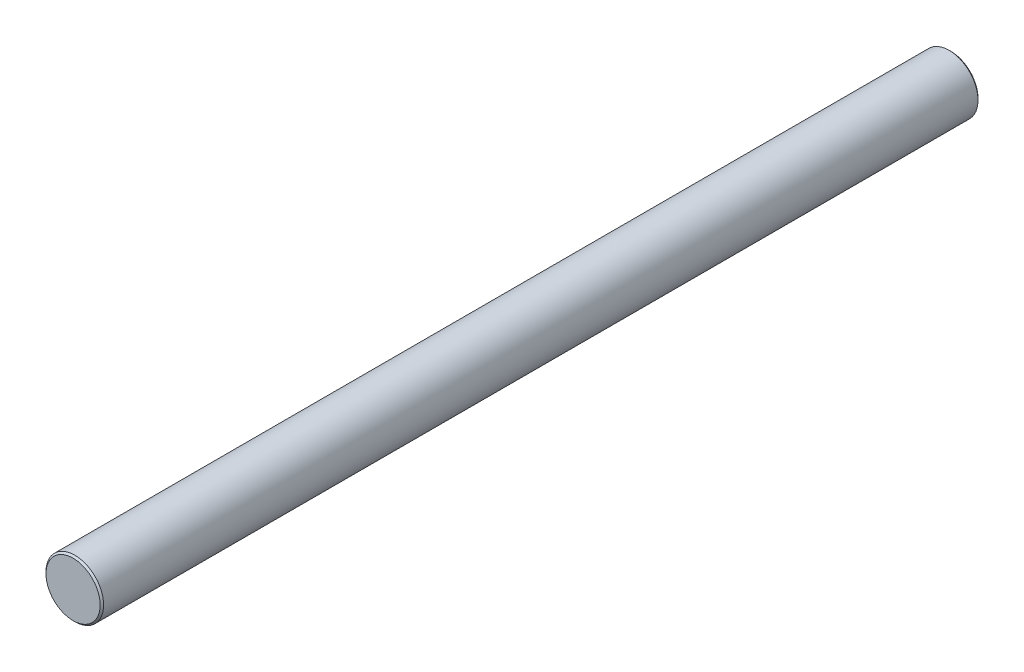
SolidWorks part; units mm, degrees
material "Alloy Steel"
ref_plane "Front Plane" through (0, 0, 0) normal (0, 0, 1) x (1, 0, 0)
ref_plane "Top Plane" through (0, 0, 0) normal (0, 1, 0) x (1, 0, 0)
ref_plane "Right Plane" through (0, 0, 0) normal (1, 0, 0) x (0, 0, -1)
sketch "Sketch1" plane through (0, 0, 0) normal (1, 0, 0) x (0, 0, -1)
  line L0 (152.4, 0) -> (-152.4, 0) construction
  line L1 (-152.4, -10) -> (-152.4, 10) construction
  point P4 (0, 0)
  point P8 (-152.4, 0)
  dimension "Length" = 304.8
  dimension "Diameter" = 20
sketch "Sketch2" plane through (0, 0, 0) normal (1, 0, 0) x (0, 0, -1)
  line L0 (-152.4, 0) -> (-152.4, 10)
  line L1 (-152.4, 10) -> (152.4, 10)
  line L2 (152.4, 10) -> (152.4, 0)
  line L3 (152.4, 0) -> (-152.4, 0)
revolve "Revolve1" add sketch "Sketch2" angle 360 about L3
chamfer "Chamfer1" distance 0.6 angle 45 2 edges at (0, 10, -152.4) (0, 10, 152.4)
sketch "Sketch3" plane through (0, 0, 0) normal (1, 0, 0) x (0, 0, -1)
  line L0 (152.4, 0) -> (-152.4, 0) construction
  line L1 (-152.4, 10) -> (152.4, 10) construction
  point P0 (-129.4, 0)
  point P1 (129.4, 0)
  point P4 (-121.7333, 0)
  point P5 (125.8419, 0)
  point P6 (-152.4, 10)
  point P13 (152.4, 10)
  dimension "Length" = 304.8
  dimension "D1" = 23
  dimension "D2" = 23
  dimension "D3" = 30.6667
  dimension "D4" = 26.5581
sketch "Sketch4" plane through (0, 0, 0) normal (0, 0, 1) x (1, 0, 0)
  line L0 (10, 0) -> (-10, 0) construction
  point P4 (0, 0)
  dimension "Diameter" = 20
equation "\"D1@Chamfer1\"=\"Diameter@Sketch1\"*.03"
equation "\"D1@Sketch3\"=\"Diameter@Sketch1\"*1.15"
equation "\"D2@Sketch3\"=\"D1@Sketch3\""
equation "\"D3@Sketch3\"=\"D1@Sketch3\"*(4/3)"
equation "\"D4@Sketch3\"=(\"D1@Sketch3\")/(TAN(0.5236rad)*2)*4/3"
equation "\"Diameter@Sketch4\" = \"Diameter@Sketch1\""
equation "\"Length@Sketch3\"=\"Length@Sketch1\""
